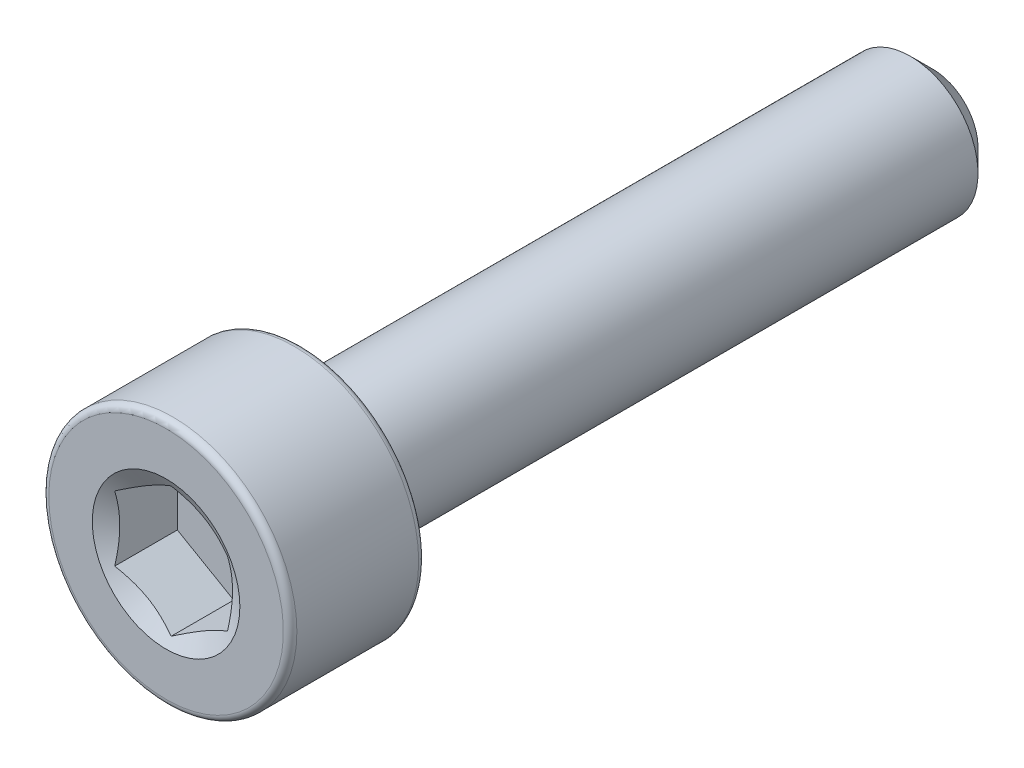
SolidWorks part; units mm, degrees
ref_plane "Front Plane" through (0, 0, 0) normal (0, 0, 1) x (1, 0, 0)
ref_plane "Top Plane" through (0, 0, 0) normal (0, 1, 0) x (1, 0, 0)
ref_plane "Right Plane" through (0, 0, 0) normal (1, 0, 0) x (0, 0, -1)
sketch "Sketch1" plane through (0, 0, 0) normal (1, 0, 0) x (0, 0, -1)
  line L0 (8.5, 0) -> (-8.5, 0) construction
  line L1 (-5.5, 2.75) -> (-5.5, -2.75) construction
  line L2 (8.5, 1.5) -> (8.5, -1.5) construction
  line L3 (8.4688, 1.5541) -> (8.7188, 1.1211) construction
  line L4 (8.6875, 1.1752) -> (8.75, 1.1752) construction
  line L5 (8.7188, 1.1211) -> (8.9688, 1.5541) construction
  line L6 (8.9688, 1.5541) -> (8.4688, 1.5541) construction
  line L7 (8.7188, 1.1752) -> (8.7188, 1.1211) construction
  line L8 (8.7188, 1.5541) -> (8.7188, 1.5) construction
  line L9 (8.9375, 1.5) -> (8.5, 1.5) construction
  point P4 (-5.5, 0)
  point P6 (-5.5, 1.25)
  point P7 (7.25, -1.5)
  point P20 (8.7188, 1.5271)
  dimension "Head Height" = 3
  dimension "Head Diameter" = 5.5
  dimension "Drive Size" = 2.5
  dimension "Length" = 14
  dimension "Thread Size" = 3
  dimension "Thread Pitch" = 0.5
  dimension "Pitch/8" = 0.0625
  dimension "Thread Note" = 1.25
sketch "Sketch2" plane through (0, 0, 0) normal (1, 0, 0) x (0, 0, -1)
  line L0 (8.5, 0) -> (8.5, 1)
  line L1 (8.5, 1.5) -> (8.5, -1.5) construction
  line L2 (8.5, 1) -> (8, 1.5)
  line L3 (8, 1.5) -> (-5.5, 1.5)
  line L4 (-5.5, 1.5) -> (-5.5, 2.6)
  line L5 (-5.65, 2.75) -> (-8.35, 2.75)
  line L6 (-8.5, 2.6) -> (-8.5, 0)
  line L7 (8.5, 0) -> (-8.5, 0) construction
  line L8 (-8.5, 0) -> (8.5, 0)
  arc A0 (-5.5, 2.6) -> (-5.65, 2.75) centre (-5.65, 2.6) ccw
  arc A1 (-8.35, 2.75) -> (-8.5, 2.6) centre (-8.35, 2.6) ccw
  point P19 (-5.5, 2.75)
  dimension "D3" = 0.15
  dimension "D1" = 0.5
  dimension "D2" = 45
revolve "Revolve1" add sketch "Sketch2" angle 360 about L0
sketch "Sketch3" plane through (0, 0, 0) normal (0, 0, 1) x (1, 0, 0)
  line L1 (-1.25, 0.7217) -> (-1.25, -0.7217)
  line L2 (-1.25, -0.7217) -> (0, -1.4434)
  line L3 (0, -1.4434) -> (1.25, -0.7217)
  line L4 (1.25, -0.7217) -> (1.25, 0.7217)
  line L5 (1.25, 0.7217) -> (0, 1.4434)
  line L6 (0, 1.4434) -> (-1.25, 0.7217)
  circle A0 centre (0, 0) radius 1.25 construction
  circle A1 centre (0, 0) radius 2.75 construction
extrude "Cut-Extrude1" cut sketch "Sketch3" against normal blind 1.5 from vertex starting at point (0, 0, 8.5)
sketch "Sketch4" plane through (0, 0, 8.5) normal (0, 0, 1) x (1, 0, 0)
  line L0 (0, 1.4434) -> (0, 1.8289) construction
  line L1 (0, 1.8289) -> (0, 2.2145) construction
  line L2 (0, 2.2145) -> (0, 2.6) construction
  circle A0 centre (0, 0) radius 1.6361
  point P12 (0, 1.6361)
extrude "Cut-Extrude2" cut sketch "Sketch4" against normal through all draft 60
split "Split1" [suppressed] bodies to split 106 112
sketch "Sketch5" [suppressed] plane through (0, 0, 0) normal (1, 0, 0) x (0, 0, -1)
  line L0 (8.6875, 1.1752) -> (8.75, 1.1752)
  line L1 (8.75, 1.1752) -> (8.9531, 1.5271)
  line L2 (8.9531, 1.5271) -> (8.4844, 1.5271)
  line L3 (8.4844, 1.5271) -> (8.6875, 1.1752)
  line L4 (8.4688, 1.5541) -> (8.7188, 1.1211) construction
sketch "Sketch6" [suppressed] plane through (0, 0, -8.5) normal (0, 0, -1) x (-1, 0, 0)
  circle A0 centre (0, 0) radius 1.5
curve "Helix/Spiral1" [suppressed] pitch 0.5 height 14.5 turns 29
sweep "Cut-Sweep1" [suppressed] cut profiles "Sketch5" path "Helix/Spiral1"
sketch "Sketch7" [suppressed] plane through (0, 0, 5.5) normal (0, 0, -1) x (-1, 0, 0)
  circle A0 centre (0, 0) radius 1.5508
  circle A1 centre (0, 0) radius 1.5 construction
  dimension "D1" = 0.0508
extrude "Boss-Extrude1" [suppressed] add sketch "Sketch7" along normal blind 1.5 draft 20 and the other way blind 0.3
equation "\"Pitch/8@Sketch1\" = \"Thread Pitch@Sketch1\" / 8"
equation "\"Thread Note@Sketch1\" = \"Thread Pitch@Sketch1\" * 2.5"
equation "\"D1@Sketch2\" = \"Thread Pitch@Sketch1\""
equation "\"D3@Sketch2\"=\"Head Height@Sketch1\"*.05"
equation "\"D1@Cut-Extrude1\" = \"Head Height@Sketch1\" * .5"
equation "\"D3@Helix/Spiral1\" = \"Length@Sketch1\" + \"Thread Pitch@Sketch1\""
equation "\"D4@Helix/Spiral1\" = \"Thread Pitch@Sketch1\""
equation "\"D2@Boss-Extrude1\" = \"Head Height@Sketch1\" * .1"
equation "\"D1\"= \"Thread Size@Sketch1\" * .4"
equation "\"D1@Boss-Extrude1\" = \"Thread Pitch@Sketch1\" * 3"
